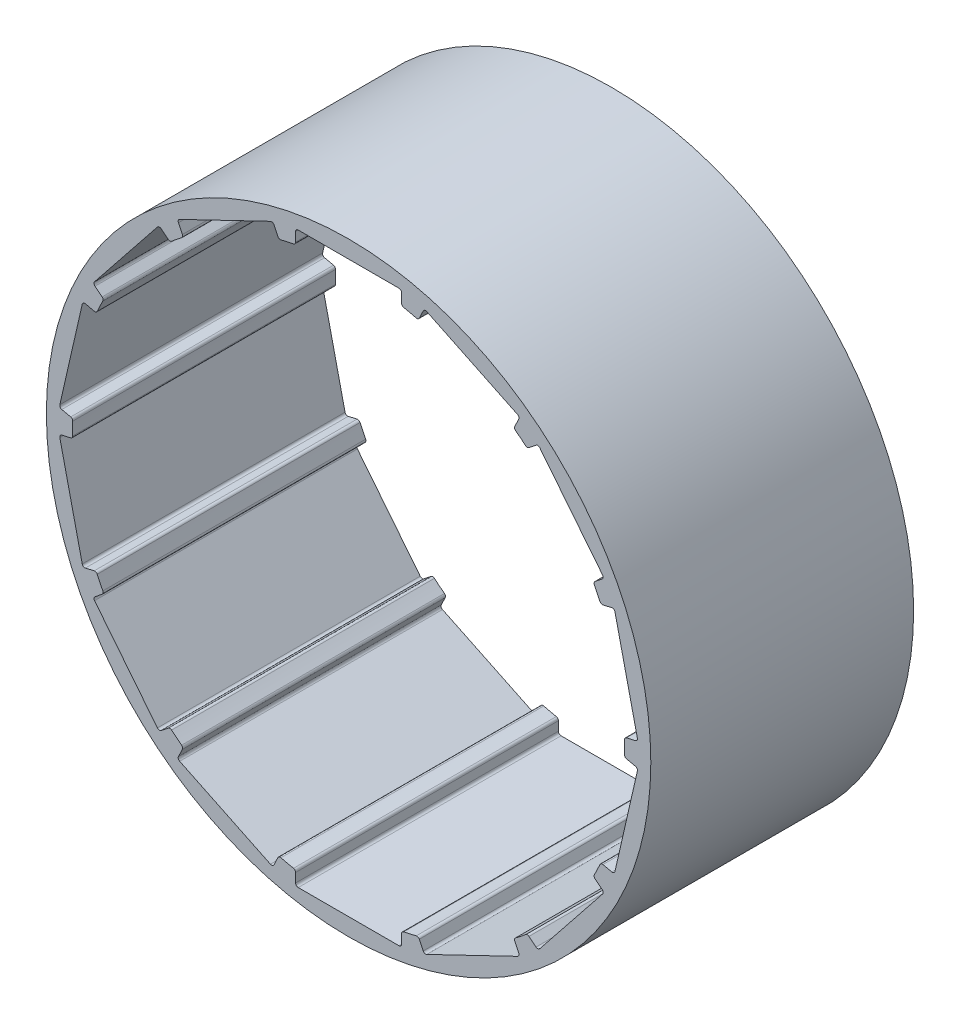
SolidWorks part; units mm, degrees
material "201 軟ｽﾃﾝﾚｽ鋼 (SS)"
ref_plane "正面" through (0, 0, 0) normal (0, 0, 1) x (1, 0, 0)
ref_plane "平面" through (0, 0, 0) normal (0, 1, 0) x (1, 0, 0)
ref_plane "右側面" through (0, 0, 0) normal (1, 0, 0) x (0, 0, -1)
ref_axis "軸1" through (0, 0, 0) along (0, 0, 1)
sketch "ｽｹｯﾁ5" plane through (0, 0, 0) normal (0, 0, 1) x (1, 0, 0)
  circle A0 centre (0, 0) radius 34.5
  circle A1 centre (0, 0) radius 31.5
  dimension "D1" = 69
  dimension "D2" = 3
extrude "ﾎﾞｽ - 押し出し3" add sketch "ｽｹｯﾁ5" along normal blind 30
sketch "ｽｹｯﾁ6" plane through (0, 0, 30) normal (0, 0, 1) x (1, 0, 0)
  line L1 (-6.05, 30.5) -> (6.05, 30.5)
  line L2 (-6.05, 30.5) -> (-6.05, 32.5)
  line L3 (-6.05, 32.5) -> (6.05, 32.5)
  line L4 (6.05, 30.5) -> (6.05, 32.5)
  line L5 (-6.05, 30.5) -> (6.05, 32.5) construction
  line L6 (-6.05, 32.5) -> (6.05, 30.5) construction
  circle A0 centre (0, 0) radius 31.5 construction
  point P0 (0, 31.5)
  dimension "D1" = 1
  dimension "D2" = 12.1
extrude "ｶｯﾄ - 押し出し1" cut sketch "ｽｹｯﾁ6" against normal through all
pattern_circular "円形ﾊﾟﾀｰﾝ4" count 14 over 360 about axis through (0, 0, 0) along (0, 0, 1) of "ｶｯﾄ - 押し出し1"
fillet "ﾌｨﾚｯﾄ1" radius 0.3 4 edges at (-6.05, 32.5, 15) (-8.6504, 31.9065, 15) (-6.05, 30.9135, 15) (-7.962, 30.4771, 15)
fillet "ﾌｨﾚｯﾄ2" radius 0.3 24 edges at (19.5521, -26.6565, 15) (18.8637, -25.2271, 15) (20.3971, -24.0044, 15) (21.6374, -24.9935, 15) (30.3389, -13.1302, 15) (29.1816, -15.5333, 15) (27.9413, -14.5442, 15) (28.7922, -12.7772, 15) (33.0314, 1.3336, 15) (31.4847, 0.9806, 15) (33.0314, -1.3336, 15) (31.4847, -0.9806, 15) (30.3389, 13.1302, 15) (28.7922, 12.7772, 15) (27.9413, 14.5442, 15) (29.1816, 15.5333, 15) (19.5521, 26.6565, 15) (21.6374, 24.9935, 15) (20.3971, 24.0044, 15) (18.8637, 25.2271, 15) (6.05, 32.5, 15) (8.6504, 31.9065, 15) (7.962, 30.4771, 15) (6.05, 30.9135, 15)
fillet "ﾌｨﾚｯﾄ3" radius 0.3 28 edges at (-21.6374, 24.9935, 15) (-19.5521, 26.6565, 15) (-18.8637, 25.2271, 15) (-20.3971, 24.0044, 15) (-27.9413, 14.5442, 15) (-29.1816, 15.5333, 15) (-30.3389, 13.1302, 15) (-28.7922, 12.7772, 15) (-33.0314, 1.3336, 15) (-31.4847, 0.9806, 15) (-31.4847, -0.9806, 15) (-33.0314, -1.3336, 15) (-29.1816, -15.5333, 15) (-30.3389, -13.1302, 15) (-28.7922, -12.7772, 15) (-27.9413, -14.5442, 15) (-19.5521, -26.6565, 15) (-21.6374, -24.9935, 15) (-18.8637, -25.2271, 15) (-20.3971, -24.0044, 15) (-8.6504, -31.9065, 15) (-6.05, -30.9135, 15) (-6.05, -32.5, 15) (-7.962, -30.4771, 15) (6.05, -32.5, 15) (6.05, -30.9135, 15) (7.962, -30.4771, 15) (8.6504, -31.9065, 15)
